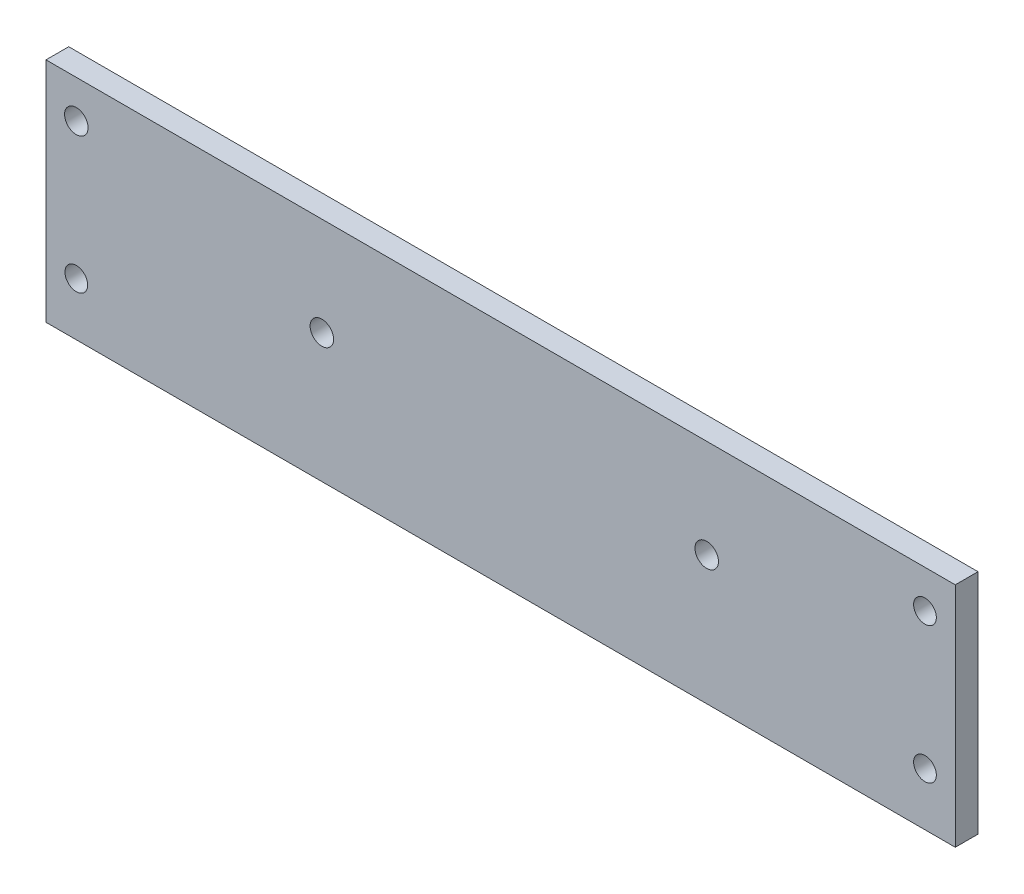
SolidWorks part; units mm, degrees
ref_plane "前视基准面" through (0, 0, 0) normal (0, 0, 1) x (1, 0, 0)
ref_plane "上视基准面" through (0, 0, 0) normal (0, 1, 0) x (1, 0, 0)
ref_plane "右视基准面" through (0, 0, 0) normal (1, 0, 0) x (0, 0, -1)
other "Configuration Table"
sketch "草图1" plane through (0, 0, 0) normal (0, 0, 1) x (1, 0, 0)
  line L1 (60, -15) -> (-60, -15)
  line L2 (60, -15) -> (60, 15)
  line L3 (60, 15) -> (-60, 15)
  line L4 (-60, -15) -> (-60, 15)
  line L5 (60, -15) -> (-60, 15) construction
  line L6 (60, 15) -> (-60, -15) construction
  point P0 (0, 0)
  dimension "D1" = 120
  dimension "D2" = 30
extrude "凸台-拉伸1" add sketch "草图1" along normal blind 3
sketch "草图3" plane through (0, 0, 0) normal (0, 0, -1) x (-1, 0, 0)
  line L2 (60, 15) -> (60, -15) construction
  line L3 (-60, 15) -> (60, 15) construction
  line L5 (-60, -15) -> (-60, 15) construction
  circle A0 centre (-56, 10) radius 1.5
  circle A1 centre (56, 10) radius 1.55
  dimension "D1" = 4
  dimension "D2" = 5
  dimension "D3" = 4
  dimension "D4" = 5
extrude "切除-拉伸2" cut sketch "草图3" against normal blind 10
sketch "草图4" plane through (0, 0, 3) normal (0, 0, 1) x (1, 0, 0)
  line L0 (0, 15) -> (0, 0) construction
  line L1 (60, 15) -> (-60, 15) construction
  line L2 (-60, -15) -> (60, -15) construction
  circle A0 centre (-26.25, -2) radius 1.55
  circle A1 centre (-26.25, -9) radius 1.55
  circle A2 centre (26.25, -9) radius 1.55
  circle A3 centre (26.25, -2) radius 1.55
  dimension "D1" = 3.1
  dimension "D2" = 3.1
  dimension "D5" = 6
  dimension "D3" = 26.25
  dimension "D4" = 26.25
  dimension "D6" = 13
sketch "草图5" plane through (0, 15, 0) normal (0, 1, 0) x (1, 0, 0)
  line L0 (0, 0) -> (0, -3) construction
  line L1 (60, -3) -> (-60, -3) construction
sketch "草图6" plane through (0, 0, 3) normal (0, 0, 1) x (1, 0, 0)
  line L0 (-56, 10) -> (-56, -8) construction
  line L1 (56, 10) -> (56, -8) construction
  circle A0 centre (-56, -8) radius 1.5
  circle A1 centre (56, -8) radius 1.5
  dimension "D1" = 3
  dimension "D2" = 18
extrude "切除-拉伸3" cut sketch "草图6" against normal blind 10
sketch "草图8" plane through (0, 0, 0) normal (0, 0, -1) x (-1, 0, 0)
  circle A0 centre (-27.1963, 2.02) radius 1.55
  circle A1 centre (23.5963, 2.02) radius 1.55
extrude "切除-拉伸4" cut sketch "草图8" against normal through all
